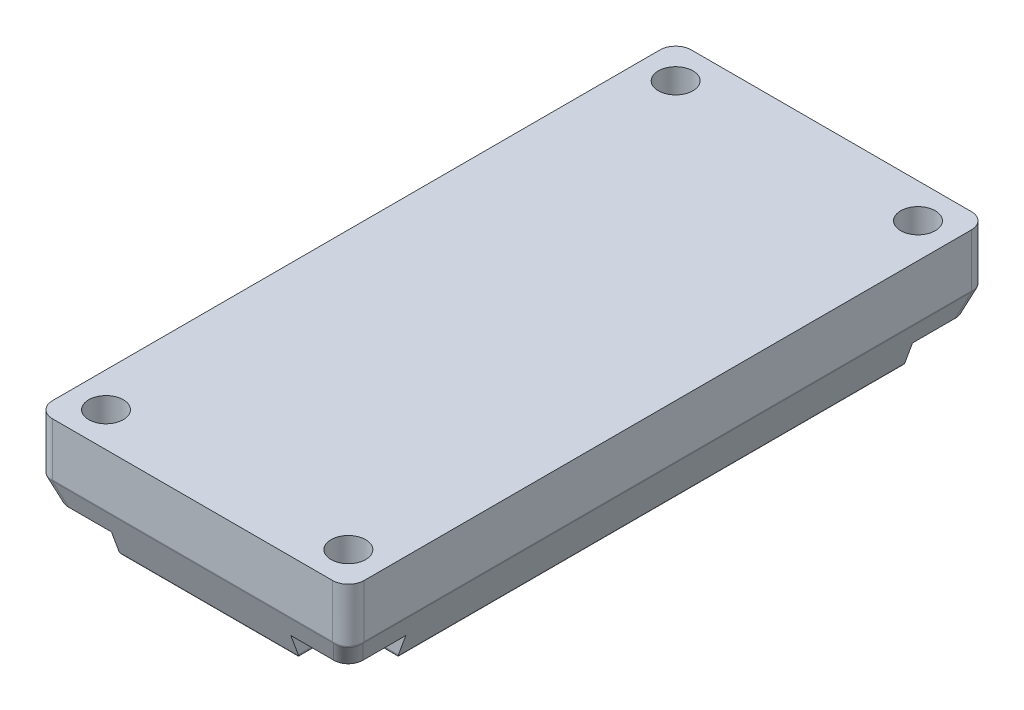
SolidWorks part; units mm, degrees
material "PC High Viscosity"
ref_plane "Front Plane" through (0, 0, 0) normal (0, 0, 1) x (1, 0, 0)
ref_plane "Top Plane" through (0, 0, 0) normal (0, 1, 0) x (1, 0, 0)
ref_plane "Right Plane" through (0, 0, 0) normal (1, 0, 0) x (0, 0, -1)
sketch "BaseS" plane through (0, 0, 0) normal (0, 1, 0) x (1, 0, 0)
  line L0 (-9.9, 20.3) -> (9.9, 20.3)
  line L1 (-9.9, 20.3) -> (-9.9, -20.3)
  line L2 (-9.9, -20.3) -> (9.9, -20.3)
  line L3 (9.9, 20.3) -> (9.9, -20.3)
  line L4 (-9.9, 20.3) -> (9.9, -20.3) construction
  line L5 (-9.9, -20.3) -> (9.9, 20.3) construction
  point P0 (0, 0)
  dimension "D1" = 19.8
  dimension "D2" = 40.6
extrude "BASE" add sketch "BaseS" along normal blind 6.4
sketch "HoleSideCutsS" plane through (0, 0, 0) normal (0, -1, 0) x (1, 0, 0)
  line L0 (-5.7, 17.9) -> (-5.7, 20.3)
  line L1 (-7.5, 16.1) -> (-9.9, 16.1)
  line L2 (-5.7, 20.3) -> (-9.9, 20.3)
  line L3 (-9.9, 20.3) -> (-9.9, 16.1)
  line L4 (-9.9, 20.3) -> (9.9, 20.3) construction
  line L5 (-9.9, -20.3) -> (-9.9, 20.3) construction
  arc A0 (-7.5, 16.1) -> (-5.7, 17.9) centre (-7.5, 17.9) ccw
  dimension "D3" = 3.6
  dimension "D1" = 4.2
extrude "HOLE SIDE CUTS" cut sketch "HoleSideCutsS" against normal blind 1.5
hole_wizard "M2 Clearance Hole1" positions "Sketch3" profile "Sketch4" hole size "M2" standard "ANSI Metric" end condition through all
sketch "Sketch3" plane through (0, 1.5, 0) normal (0, -1, 0) x (-1, 0, 0)
  line L0 (9.9, -20.3) -> (9.9, -16.1) construction
  line L1 (5.7, -20.3) -> (9.9, -20.3) construction
  point P0 (7.7, -18.1)
  dimension "D1" = 2.2
  dimension "D2" = 2.2
sketch "Sketch4" plane through (-7.7, 1.5, 18.1) normal (1, 0, 0) x (0, 0, -1)
  line L0 (0, 0) -> (0, 4.9)
  line L1 (0, 4.9) -> (1.1, 4.9)
  line L2 (1.1, 4.9) -> (1.1, 0)
  line L5 (1.1, 0) -> (0, 0)
  line L11 (0, -6.35) -> (0, 107.95) construction
  dimension "Thru Hole Dia." = 2.2
  dimension "Thru Hole Depth" = 4.9
mirror "HOLE FEATURES HM" about plane through (0, 0, 0) normal (1, 0, 0) of "M2 Clearance Hole1", "HOLE SIDE CUTS"
mirror "HOLE FEATURE VM" about plane through (0, 0, 0) normal (0, 0, 1) of "HOLE FEATURES HM", "HOLE SIDE CUTS", "M2 Clearance Hole1"
sketch "SideChamfer1S" plane through (0, 0, 0) normal (0, 0, 1) x (1, 0, 0)
  line L0 (9.9, 3) -> (9.9, 0)
  line L1 (9.9, 6.4) -> (9.9, 1.5) construction
  line L2 (9.9, 0) -> (8.8081, 0)
  line L3 (9.9, 0) -> (7.5, 0) construction
  line L4 (8.8081, 0) -> (9.9, 3)
  dimension "D1" = 3
  dimension "D2" = 20
extrude "SIDE CHAMFER 1" cut sketch "SideChamfer1S" against normal through all both and the other way through all
mirror "SC1 HM" about plane through (0, 0, 0) normal (1, 0, 0) of "SIDE CHAMFER 1"
sketch "SideChamfer2S" plane through (0, 0, 0) normal (1, 0, 0) x (0, 0, -1)
  line L0 (20.3, 3) -> (20.3, 0)
  line L1 (20.3, 6.4) -> (20.3, 3) construction
  line L2 (20.3, 0) -> (19.2081, 0)
  line L4 (19.2081, 0) -> (20.3, 3)
  dimension "D1" = 3
  dimension "D2" = 20
extrude "SIDE CHAMFER 2" cut sketch "SideChamfer2S" against normal through all both and the other way through all
mirror "SC2 VM" about plane through (0, 0, 0) normal (0, 0, 1) of "SIDE CHAMFER 2"
fillet "BASE F" radius 1 8 edges at (-9.627, 2.25, -20.027) (-9.9, 4.7, -20.3) (9.627, 2.25, -20.027) (9.9, 4.7, -20.3) (-9.627, 2.25, 20.027) (-9.9, 4.7, 20.3) (9.627, 2.25, 20.027) (9.9, 4.7, 20.3)
fillet "BASE BOTTOM F" radius 0.2 32 edges at (9.8996, 2.9988, -19.3293) (9.6071, 2.9341, -20.0071) (8.9293, 2.9988, -20.2996) (0, 3, -20.3) (-8.9293, 2.9988, -20.2996) (-9.6071, 2.9341, -20.0071) (-9.8996, 2.9988, -19.3293) (-9.9, 3, 0) (-9.8996, 2.9988, 19.3293) (-9.6071, 2.9341, 20.0071) (-8.9293, 2.9988, 20.2996) (0, 3, 20.3) (8.9293, 2.9988, 20.2996) (9.6071, 2.9341, 20.0071) (9.8996, 2.9988, 19.3293) (5.7, 0, 18.554) (6.2272, 0, 16.6272) (8.154, 0, 16.1) (8.8081, 0, 0) (8.154, 0, -16.1) (6.2272, 0, -16.6272) (5.7, 0, -18.554) (0, 0, -19.2081) (-5.7, 0, -18.554) (-6.2272, 0, -16.6272) (-8.154, 0, -16.1) (-8.8081, 0, 0) (-8.154, 0, 16.1) (-6.2272, 0, 16.6272) (-5.7, 0, 18.554) (0, 0, 19.2081) (9.9, 3, 0)
